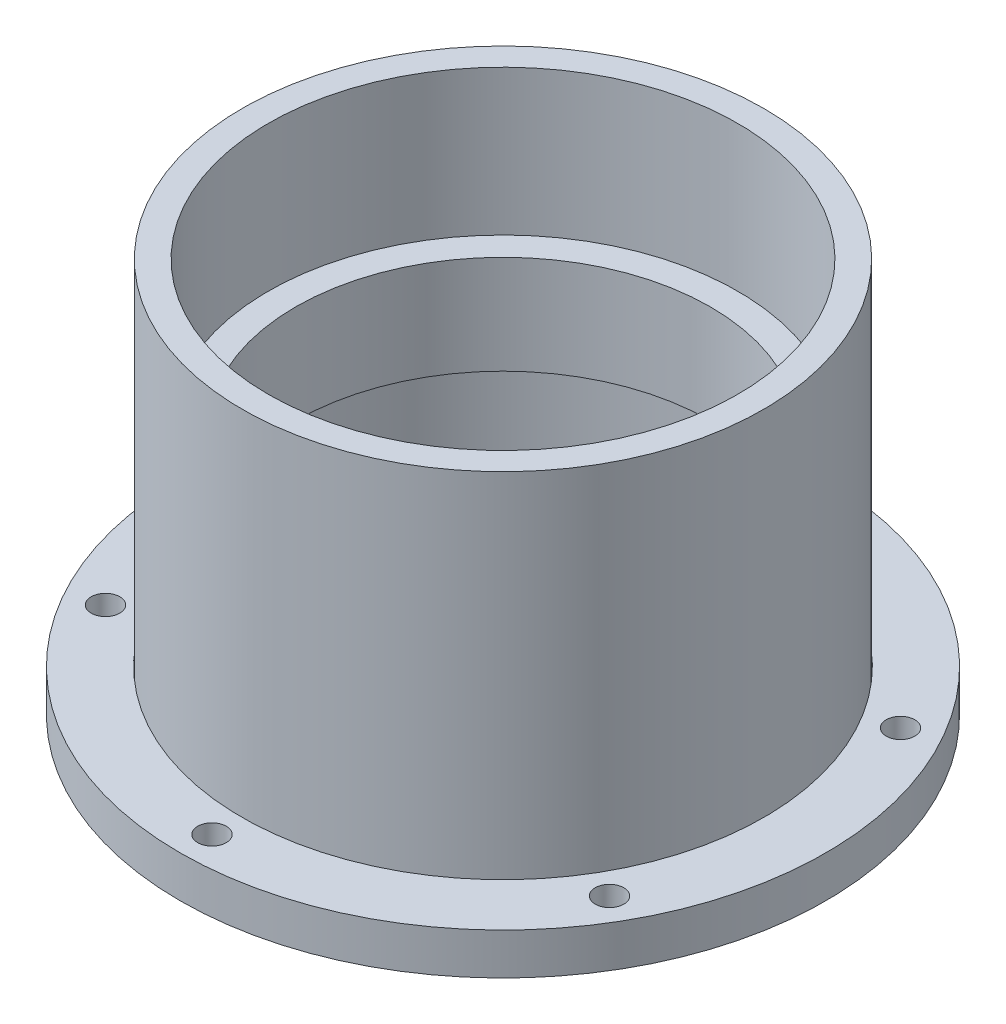
SolidWorks part; units mm, degrees
ref_plane "Front Plane" through (0, 0, 0) normal (0, 0, 1) x (1, 0, 0)
ref_plane "Top Plane" through (0, 0, 0) normal (0, 1, 0) x (1, 0, 0)
ref_plane "Right Plane" through (0, 0, 0) normal (1, 0, 0) x (0, 0, -1)
sketch "Sketch2" plane through (0, 0, 0) normal (0, 1, 0) x (1, 0, 0)
  circle A0 centre (0, 0) radius 45.22
  circle A1 centre (0, 0) radius 50.22
extrude "Boss-Extrude1" add sketch "Sketch2" along normal blind 29
sketch "Sketch3" plane through (0, 29, 0) normal (0, 1, 0) x (1, 0, 0)
  circle A0 centre (0, 0) radius 50.22
  circle A1 centre (0, 0) radius 39.97
  circle A3 centre (0, 0) radius 45.22
  circle M4 centre (0, 0) radius 50.22
  circle M5 centre (0, 0) radius 45.22
extrude "Boss-Extrude2" add sketch "Sketch3" along normal blind 19 contours A1 M5 | M4 M5 region at (-48.7996, 29, 0) region at (-43.941, 29, 0)
sketch "Sketch4" plane through (0, 48, 0) normal (0, 1, 0) x (1, 0, 0)
  circle A0 centre (0, 0) radius 50.22
  circle A1 centre (0, 0) radius 45.22
extrude "Boss-Extrude3" add sketch "Sketch4" along normal blind 28
sketch "Sketch6" plane through (0, 0, 0) normal (0, -1, 0) x (1, 0, 0)
  circle A0 centre (0, 0) radius 62.2
  circle A1 centre (0, 0) radius 50.32
  circle A2 centre (0, 56.06) radius 2.75
  circle A3 centre (0, 0) radius 45.22 construction
  circle A4 centre (-48.5494, 28.03) radius 2.75
  circle A5 centre (-48.5494, -28.03) radius 2.75
  circle A6 centre (48.5494, 28.03) radius 2.75
  circle A7 centre (48.5494, -28.03) radius 2.75
  circle A8 centre (0, -56.06) radius 2.75
  dimension "D1" = 11.88
  dimension "D2" = 56.06
extrude "Boss-Extrude4" add sketch "Sketch6" against normal blind 8
